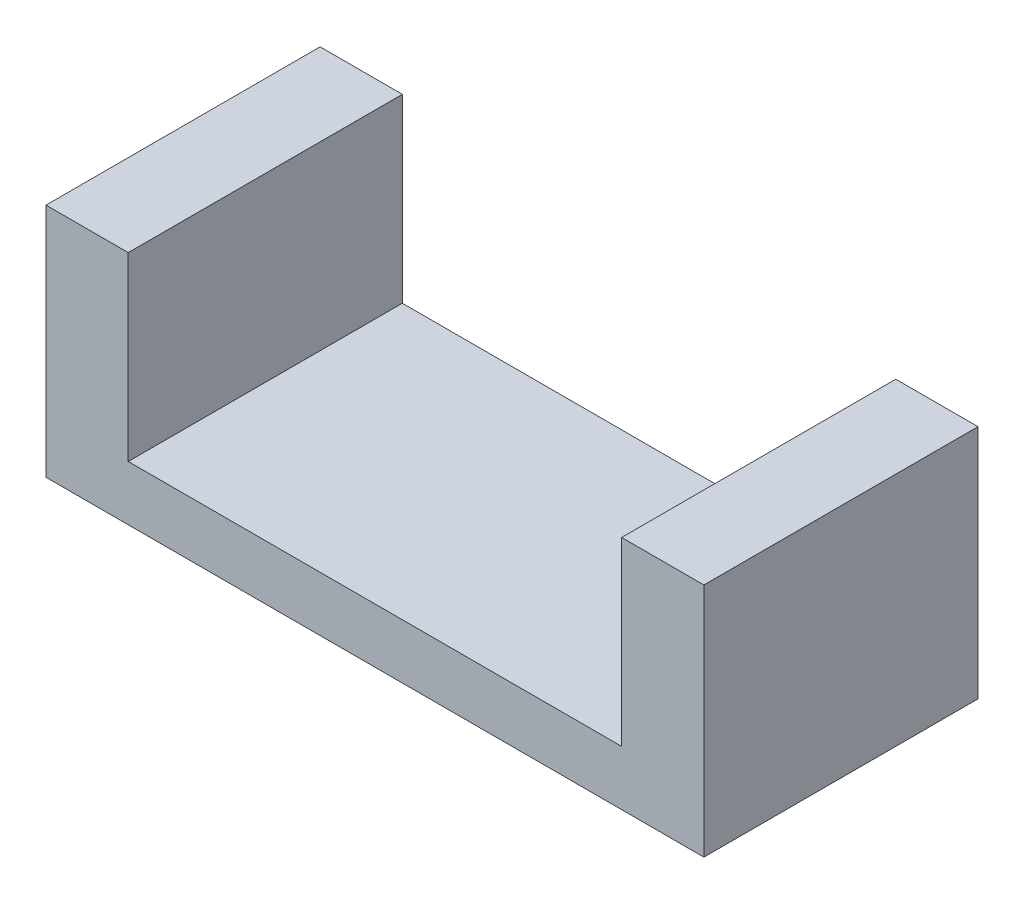
SolidWorks part; units mm, degrees
ref_plane "前视基准面" through (0, 0, 0) normal (0, 0, 1) x (1, 0, 0)
ref_plane "上视基准面" through (0, 0, 0) normal (0, 1, 0) x (1, 0, 0)
ref_plane "右视基准面" through (0, 0, 0) normal (1, 0, 0) x (0, 0, -1)
sketch "草图1" plane through (0, 0, 0) normal (0, 1, 0) x (1, 0, 0)
  line L1 (4.5, -2.5) -> (-4.5, -2.5)
  line L2 (4.5, -2.5) -> (4.5, 2.5)
  line L3 (4.5, 2.5) -> (-4.5, 2.5)
  line L4 (-4.5, -2.5) -> (-4.5, 2.5)
  line L5 (4.5, -2.5) -> (-4.5, 2.5) construction
  line L6 (4.5, 2.5) -> (-4.5, -2.5) construction
  line L7 (6, -2.5) -> (-6, -2.5)
  line L8 (6, -2.5) -> (6, 2.5)
  line L9 (6, 2.5) -> (-6, 2.5)
  line L10 (-6, -2.5) -> (-6, 2.5)
  line L11 (6, -2.5) -> (-6, 2.5) construction
  line L12 (6, 2.5) -> (-6, -2.5) construction
  point P0 (0, 0)
  point P6 (0, 0)
  dimension "D1" = 9
  dimension "D2" = 5
  dimension "D3" = 12
extrude "凸台-拉伸1" add sketch "草图1" along normal blind 1 contours L4 L1 L2 L3 region at (0, 0, 0)
extrude "凸台-拉伸2" add sketch "草图1<3>" along normal blind 4.3 contours L8 L9 L2 L7 | L10 L7 L4 L9 region at (5.25, 0, 0) region at (-5.25, 0, 0)
sketch "草图1<3>" plane through (0, 0, 0) normal (0, 1, 0) x (1, 0, 0) same geometry as "草图1"
